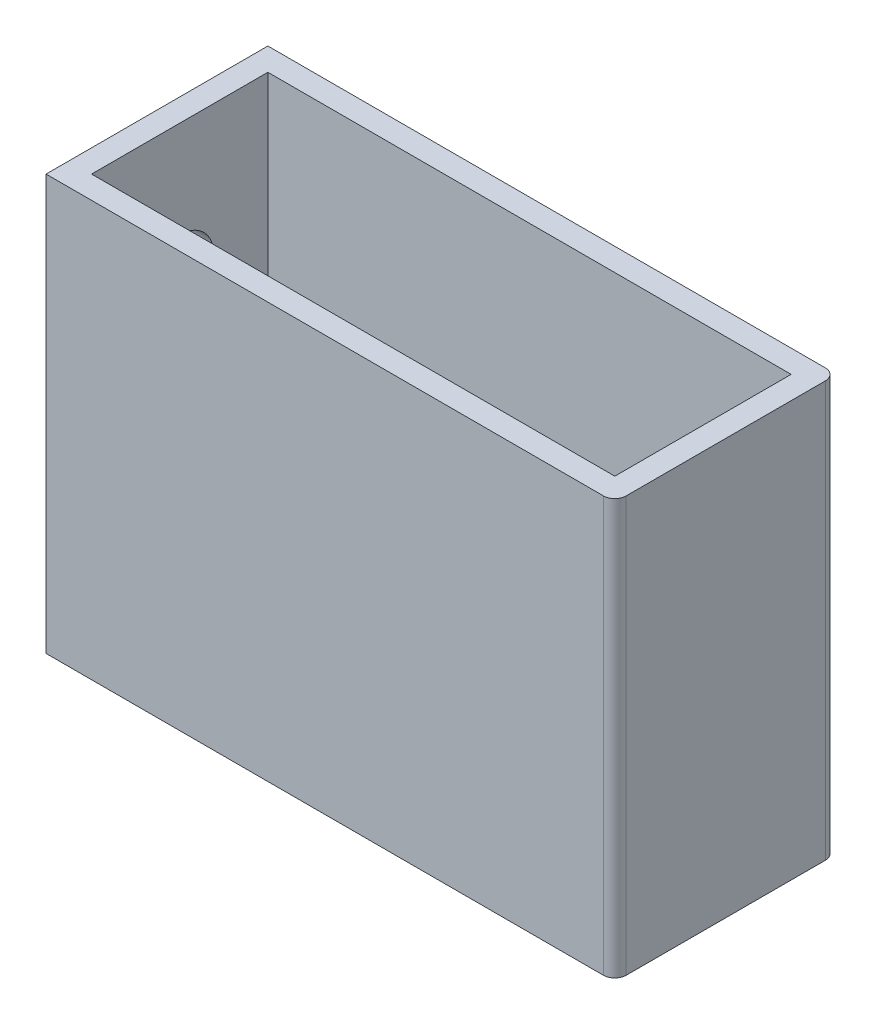
SolidWorks part; units mm, degrees
ref_plane "Front Plane" through (0, 0, 0) normal (0, 0, 1) x (1, 0, 0)
ref_plane "Top Plane" through (0, 0, 0) normal (0, 1, 0) x (1, 0, 0)
ref_plane "Right Plane" through (0, 0, 0) normal (1, 0, 0) x (0, 0, -1)
sketch "Sketch1" plane through (0, 0, 0) normal (0, 1, 0) x (1, 0, 0)
  line L0 (-46, 15.5) -> (-46, -15.5)
  line L1 (-50, 19.5) -> (50, 19.5)
  line L2 (-50, 19.5) -> (-50, -19.5)
  line L3 (-50, -19.5) -> (50, -19.5)
  line L4 (50, 19.5) -> (50, -19.5)
  line L5 (-50, 19.5) -> (50, -19.5) construction
  line L6 (-50, -19.5) -> (50, 19.5) construction
  line L7 (-46, -15.5) -> (46, -15.5)
  line L8 (46, 15.5) -> (46, -15.5)
  line L9 (-46, 15.5) -> (46, 15.5)
  point P0 (0, 0)
  dimension "D1" = 39
  dimension "D2" = 100
  dimension "D3" = 4
extrude "Boss-Extrude2" add sketch "Sketch1" along normal blind 3 contours L9 L0 L7 L8 region at (0, 0, 0)
extrude "Boss-Extrude3" add sketch "Sketch1<3>" along normal blind 73
sketch "Sketch1<3>" plane through (0, 0, 0) normal (0, 1, 0) x (1, 0, 0) same geometry as "Sketch1"
fillet "Fillet1" radius 2 1 edges at (50, 36.5, 19.5)
fillet "Fillet2" radius 2 1 edges at (50, 36.5, -19.5)
sketch "Sketch3" plane through (0, 3, 0) normal (0, 1, 0) x (1, 0, 0)
  line L0 (-46, 15.5) -> (46, 15.5) construction
  line L1 (46, -15.5) -> (38.86, -15.5)
  line L2 (46, -15.5) -> (46, 15.5)
  line L3 (46, 15.5) -> (38.86, 15.5)
  line L4 (38.86, -15.5) -> (38.86, 15.5)
  dimension "D1" = 7.14
extrude "Boss-Extrude4" add sketch "Sketch3" along normal blind 28
sketch "Sketch4" plane through (0, 31, 0) normal (0, 1, 0) x (1, 0, 0)
  line L0 (38.86, -7.08) -> (38.86, -9.931)
  line L1 (38.86, -7.08) -> (46, -7.08)
  line L2 (46, -15.5) -> (46, 15.5) construction
  line L3 (38.86, 15.5) -> (38.86, -15.5) construction
  line L4 (38.86, -9.931) -> (46, -9.931)
  line L5 (46, -9.931) -> (46, -7.08)
  circle A0 centre (43.36, 8.92) radius 0.5
  circle A1 centre (43.36, -1.08) radius 0.5
  line M9 (46, -15.5) -> (46, 15.5)
  line M11 (38.86, 15.5) -> (38.86, -15.5)
extrude "Boss-Extrude5" add sketch "Sketch4" along normal blind 4 contours L4 L1 M11 M9 region at (42.43, 31, 8.5055)
sketch "Sketch5" plane through (0, 31, 0) normal (0, 1, 0) x (1, 0, 0)
  line L4 (46, -15.5) -> (46, -9.931)
  line L5 (46, -9.931) -> (38.86, -9.931)
  line L6 (38.86, -9.931) -> (38.86, -15.5)
  line L7 (38.86, -15.5) -> (46, -15.5)
  line L8 (46, -15.5) -> (46, -9.931)
  line L9 (46, -9.931) -> (38.86, -9.931)
  line L10 (38.86, -9.931) -> (38.86, -15.5)
  line L11 (38.86, -15.5) -> (46, -15.5)
  dimension "D1" = 0
extrude "Cut-Extrude1" cut sketch "Sketch5" against normal blind 28
extrude "Cut-Extrude3" cut sketch "Sketch4<3>" against normal blind 20 contours A1 | A0
sketch "Sketch4<3>" plane through (0, 31, 0) normal (0, 1, 0) x (1, 0, 0) same geometry as "Sketch4"
pattern_linear "LPattern5" count 2 spacing 47.64 along (-1, 0, 0) of "Boss-Extrude4", "Boss-Extrude5", "Cut-Extrude1"
pattern_linear "LPattern6" count 2 spacing 49 along (-1, 0, 0) of "Cut-Extrude3"
sketch "Sketch10" plane through (38.86, 0, 0) normal (-1, 0, 0) x (0, 0, 1)
  line L1 (7.08, 35) -> (9.931, 35)
  line L2 (7.08, 35) -> (7.08, 3)
  line L3 (7.08, 3) -> (9.931, 3)
  line L4 (9.931, 35) -> (9.931, 3)
extrude "Boss-Extrude6" add sketch "Sketch10" along normal blind 41
sketch "Sketch12" plane through (-46, 0, 0) normal (1, 0, 0) x (0, 0, -1)
  line L1 (15.5, 73) -> (15.5, 3) construction
  line L2 (15.5, 50) -> (-15.5, 50)
  line L3 (-15.5, 73) -> (-15.5, 3) construction
  circle A0 centre (0, 50) radius 6
extrude "Cut-Extrude4" cut sketch "Sketch12" against normal blind 10 contours L2 A0 | L2 A0 region at (-46, 47.4535, 0) region at (-46, 52.5465, 0)
